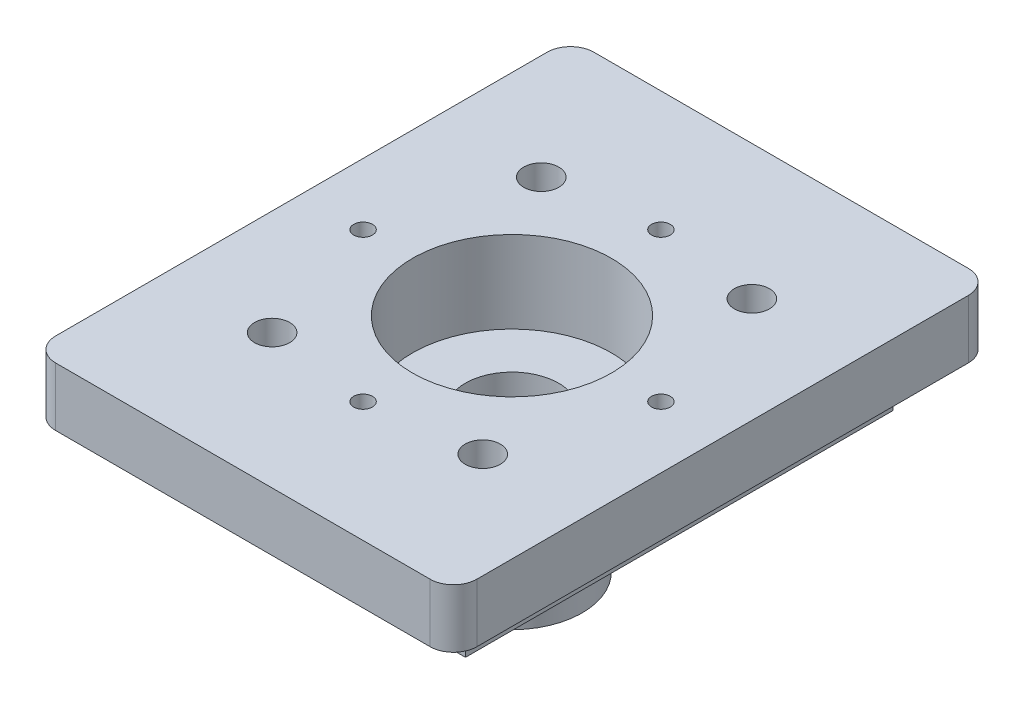
SolidWorks part; units mm, degrees
ref_plane "Front Plane" through (0, 0, 0) normal (0, 0, 1) x (1, 0, 0)
ref_plane "Top Plane" through (0, 0, 0) normal (0, 1, 0) x (1, 0, 0)
ref_plane "Right Plane" through (0, 0, 0) normal (1, 0, 0) x (0, 0, -1)
sketch "Sketch1" plane through (0, 0, 0) normal (0, 1, 0) x (1, 0, 0)
  line L1 (-19.9858, 28.651) -> (25.7342, 28.651)
  line L2 (-19.9858, 28.651) -> (-19.9858, -29.769)
  line L3 (-19.9858, -29.769) -> (25.7342, -29.769)
  line L4 (25.7342, 28.651) -> (25.7342, -29.769)
  dimension "D1" = 58.42
  dimension "D2" = 45.72
extrude "Boss-Extrude1" add sketch "Sketch1" along normal blind 6.35
sketch "Sketch2" plane through (0, 6.35, 0) normal (0, 1, 0) x (1, 0, 0)
  line L1 (25.7342, 28.651) -> (-19.9858, 28.651) construction
  line L3 (-19.9858, -0.559) -> (25.7342, -0.559) construction
  line L4 (-19.9858, 28.651) -> (-19.9858, -29.769) construction
  line L5 (25.7342, -29.769) -> (25.7342, 28.651) construction
  line L9 (-19.9858, -0.559) -> (2.8742, 28.651) construction
  line L10 (2.8742, 28.651) -> (25.7342, -0.559) construction
  circle A0 centre (-8.5558, 14.046) radius 1.905
  circle A1 centre (14.3042, 14.046) radius 1.905
  circle A2 centre (-8.5558, -15.164) radius 1.905
  circle A3 centre (14.3042, -15.164) radius 1.905
  dimension "D2" = 3.81
  dimension "D3" = 3.81
  dimension "D4" = 3.81
  dimension "D5" = 3.81
  dimension "D1" = 18.5459
  dimension "D6" = 29.21
  dimension "D7" = 29.21
  dimension "D8" = 22.86
  dimension "D9" = 22.86
sketch "Sketch3" plane through (0, 0, 0) normal (0, -1, 0) x (1, 0, 0)
  line L1 (-15.2895, 23.7683) -> (21.0379, 23.7683)
  line L2 (-15.2895, 23.7683) -> (-15.2895, -22.6502)
  line L3 (-15.2895, -22.6502) -> (21.0379, -22.6502)
  line L4 (21.0379, 23.7683) -> (21.0379, -22.6502)
  dimension "D1" = 7.62
  dimension "D2" = 7.62
extrude "Cut-Extrude1" cut sketch "Sketch2" against normal through all
extrude "Boss-Extrude2" add sketch "Sketch3" along normal blind 5.08
sketch "Sketch4" plane through (0, -5.08, 0) normal (0, -1, 0) x (1, 0, 0)
  line L0 (-19.9858, 0.559) -> (25.7342, 0.559) construction
  line L1 (-19.9858, -28.651) -> (-19.9858, 29.769) construction
  line L2 (25.7342, 29.769) -> (25.7342, -28.651) construction
  line L3 (2.8742, 29.769) -> (2.8742, -28.651) construction
  line L4 (-19.9858, 29.769) -> (25.7342, 29.769) construction
  line L5 (25.7342, -28.651) -> (-19.9858, -28.651) construction
  circle A0 centre (2.8742, 0.559) radius 7.62
  circle A1 centre (2.8742, 0.559) radius 5.08
  dimension "D1" = 10.16
  dimension "D2" = 15.24
extrude "Boss-Extrude3" add sketch "Sketch4" along normal blind 12.7
fillet "Fillet1" radius 2.54 4 edges at (25.7342, 3.175, -28.651) (-19.9858, 3.175, -28.651) (-19.9858, 3.175, 29.769) (25.7342, 3.175, 29.769)
sketch "Sketch5" plane through (0, 6.35, 0) normal (0, 1, 0) x (1, 0, 0)
  line L0 (-8.5558, 14.046) -> (14.3042, -15.164) construction
  circle A0 centre (2.8742, -0.559) radius 10.795
  point P6 (0, 0)
  point P7 (2.8742, -0.559)
  dimension "D1" = 21.59
extrude "Cut-Extrude2" cut sketch "Sketch5" against normal blind 8.89
sketch "Sketch6" plane through (0, 6.35, 0) normal (0, 1, 0) x (1, 0, 0)
  line L0 (2.8742, 15.6054) -> (-13.2903, -0.559) construction
  line L1 (-13.2903, -0.559) -> (2.8742, -16.7235) construction
  line L2 (2.8742, -16.7235) -> (19.0387, -0.559) construction
  line L3 (19.0387, -0.559) -> (2.8742, 15.6054) construction
  circle A4 centre (2.8742, 15.6054) radius 1.016
  circle A5 centre (-13.2903, -0.559) radius 1.016
  circle A6 centre (2.8742, -16.7235) radius 1.016
  circle A7 centre (19.0387, -0.559) radius 1.016
  circle A8 centre (2.8742, -16.7235) radius 1.016
  point P12 (2.8742, -0.559)
  point P13 (0, 0)
  dimension "D1" = 2.032
  dimension "D2" = 2.032
  dimension "D3" = 2.032
  dimension "D4" = 2.032
  dimension "D5" = 2.032
  dimension "D6" = 22.86
  dimension "D7" = 90
  dimension "D8" = 90
  dimension "D9" = 90
extrude "Cut-Extrude3" cut sketch "Sketch6" against normal blind 19.05 contours A5 | A4 | A7 | A6 region at (2.8742, 6.35, -15.6054) region at (-13.2903, 6.35, 0.559) region at (2.8742, 6.35, 16.7235) region at (19.0387, 6.35, 0.559)
extrude "Cut-Extrude4" cut sketch "Sketch4<2>" against normal blind 19.05 contours A1 region at (2.8742, -5.08, 0.559)
sketch "Sketch4<2>" plane through (0, -5.08, 0) normal (0, -1, 0) x (1, 0, 0) same geometry as "Sketch4"
